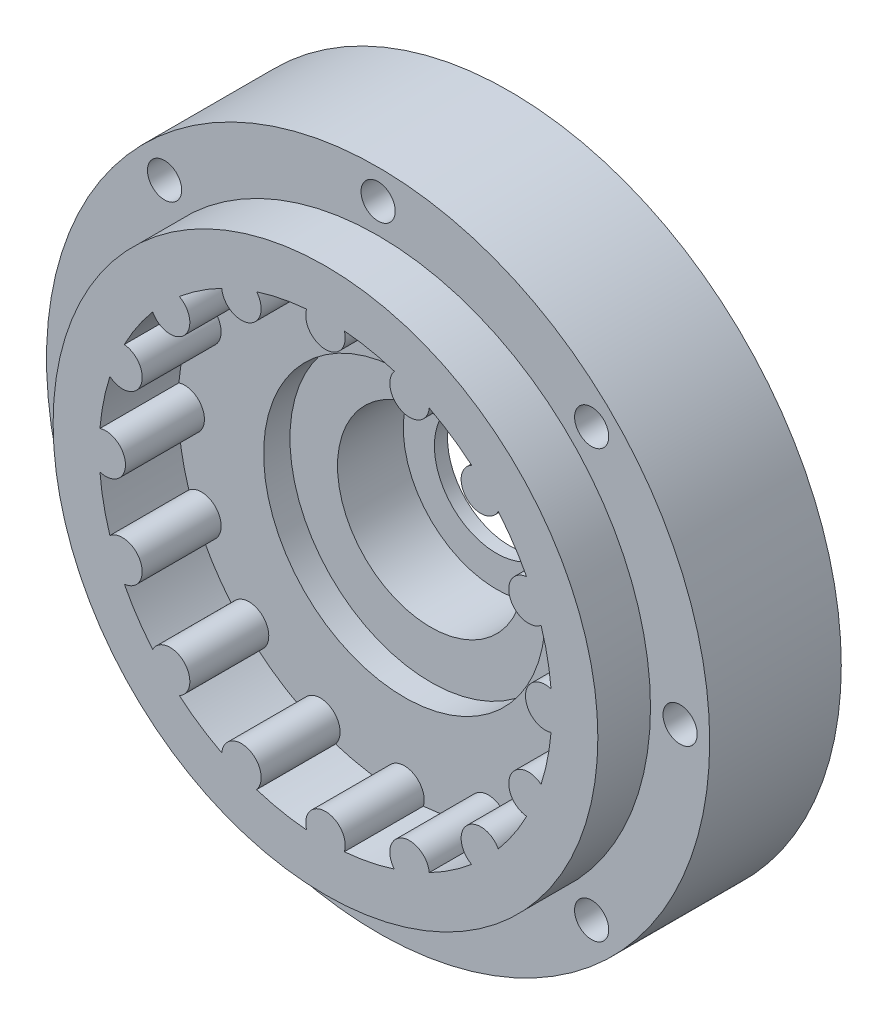
SolidWorks part; units mm, degrees
material "ABS"
ref_plane "Front Plane" through (0, 0, 0) normal (0, 0, 1) x (1, 0, 0)
ref_plane "Top Plane" through (0, 0, 0) normal (0, 1, 0) x (1, 0, 0)
ref_plane "Right Plane" through (0, 0, 0) normal (1, 0, 0) x (0, 0, -1)
sketch "Sketch1" plane through (0, 0, 0) normal (0, 0, 1) x (1, 0, 0)
  circle A0 centre (0, 0) radius 32.004
  dimension "D1" = 64.008
extrude "Boss-Extrude1" add sketch "Sketch1" along normal blind 12.7
sketch "Sketch2" plane through (0, 0, 12.7) normal (0, 0, 1) x (1, 0, 0)
  circle A0 centre (0, 0) radius 26.289
  circle A1 centre (0, 0) radius 32.004
  circle A2 centre (0, 0) radius 32.004
  dimension "D1" = 0
  dimension "D2" = 5.715
extrude "Cut-Extrude1" cut sketch "Sketch2" against normal blind 2.54 flip side to cut
sketch "Sketch3" plane through (0, 0, 10.16) normal (0, 0, 1) x (1, 0, 0)
  line L0 (0, 0) -> (0, 21.209) construction
  circle A1 centre (0, 21.209) radius 1.905
  circle A3 centre (0, 0) radius 21.209 construction
  circle A13 centre (8.1163, 19.5946) radius 1.905
  circle A14 centre (14.997, 14.997) radius 1.905
  circle A15 centre (19.5946, 8.1163) radius 1.905
  circle A16 centre (21.209, 0) radius 1.905
  circle A17 centre (19.5946, -8.1163) radius 1.905
  circle A18 centre (14.997, -14.997) radius 1.905
  circle A19 centre (8.1163, -19.5946) radius 1.905
  circle A20 centre (0, -21.209) radius 1.905
  circle A21 centre (-8.1163, -19.5946) radius 1.905
  circle A22 centre (-14.997, -14.997) radius 1.905
  circle A23 centre (-19.5946, -8.1163) radius 1.905
  circle A24 centre (-21.209, 0) radius 1.905
  circle A25 centre (-19.5946, 8.1163) radius 1.905
  circle A26 centre (-14.997, 14.997) radius 1.905
  circle A27 centre (-8.1163, 19.5946) radius 1.905
  dimension "D2" = 3.81
  dimension "D3" = 16
  dimension "D1" = 42.418
  dimension "D4" = 21.209
sketch "Sketch4" plane through (0, 0, 10.16) normal (0, 0, 1) x (1, 0, 0)
  circle A39 centre (0, 0) radius 27.559 construction
  circle A40 centre (0, 0) radius 13.589
  circle A41 centre (0, 0) radius 26.289 construction
  dimension "D2" = 55.118
  dimension "D1" = 13.97
extrude "Cut-Extrude3" cut sketch "Sketch4" against normal blind 2.54 contours A40 region at (0, 0, 10.16)
sketch "Sketch5" plane through (0, 0, 7.62) normal (0, 0, 1) x (1, 0, 0)
  circle A0 centre (0, 0) radius 9
  circle A1 centre (0, 0) radius 6
  dimension "D1" = 18
  dimension "D2" = 12
extrude "Cut-Extrude4" cut sketch "Sketch5" against normal through all contours A1 region at (0, 0, 7.62)
sketch "Sketch6" plane through (0, 0, 12.7) normal (0, 0, 1) x (1, 0, 0)
  line L0 (0, 0) -> (0, 32.004) construction
  line L1 (0, 0) -> (22.6302, 22.6302) construction
  line L2 (0, 0) -> (32.004, 0) construction
  line L3 (0, 0) -> (22.6302, -22.6302) construction
  line L4 (0, 0) -> (0, -32.004) construction
  line L5 (0, 0) -> (-22.6302, -22.6302) construction
  line L6 (0, 0) -> (-32.004, 0) construction
  line L7 (0, 0) -> (-22.6302, 22.6302) construction
  line L8 (0, 0) -> (0, 29.1465) construction
  circle A0 centre (0, 0) radius 32.004 construction
  point P6 (0, 29.1465)
  point P16 (20.6097, 20.6097)
  point P18 (29.1465, 0)
  point P20 (20.6097, -20.6097)
  point P22 (0, -29.1465)
  point P24 (-20.6097, -20.6097)
  point P26 (-29.1465, 0)
  point P28 (-20.6097, 20.6097)
  dimension "D1" = 29.1465
  dimension "D2" = 8
hole_wizard "M4x0.7 Tapped Hole1" positions "Sketch6" profile "Sketch7" tap size "M4x0.7" standard "ANSI Metric" end condition through all
sketch "Sketch7" plane through (-20.6097, 20.6097, 12.7) normal (1, 0, 0) x (0, -1, 0)
  line L0 (0, 0) -> (0, 12.7)
  line L1 (0, 12.7) -> (1.65, 12.7)
  line L2 (1.65, 12.7) -> (1.65, 0)
  line L5 (1.65, 0) -> (0, 0)
  line L11 (0, -6.35) -> (0, 107.95) construction
  dimension "Thru Tap Drill Dia." = 3.3
  dimension "Thru Tap Drill Depth" = 12.7
cosmetic thread "Hole Thread1" parameters "D2"=4
cosmetic thread "Hole Thread2" parameters "D2"=4
cosmetic thread "Hole Thread3" parameters "D2"=4
cosmetic thread "Hole Thread4" parameters "D2"=4
cosmetic thread "Hole Thread5" parameters "D2"=4
cosmetic thread "Hole Thread6" parameters "D2"=4
cosmetic thread "Hole Thread7" parameters "D2"=4
cosmetic thread "Hole Thread8" parameters "D2"=4
extrude "Cut-Extrude5" cut sketch "Sketch5<3>" against normal blind 6.35
sketch "Sketch5<3>" plane through (0, 0, 7.62) normal (0, 0, 1) x (1, 0, 0) same geometry as "Sketch5"
sketch "Sketch8" plane through (0, 0, 10.16) normal (0, 0, 1) x (1, 0, 0)
  circle A0 centre (0, 0) radius 21.844
  circle A1 centre (0, 0) radius 26.289
  circle A5 centre (0, 0) radius 26.289
  dimension "D1" = 0
extrude "Boss-Extrude2" add sketch "Sketch8" along normal blind 7.62
extrude "Boss-Extrude3" add sketch "Sketch3" along normal blind 7.62
